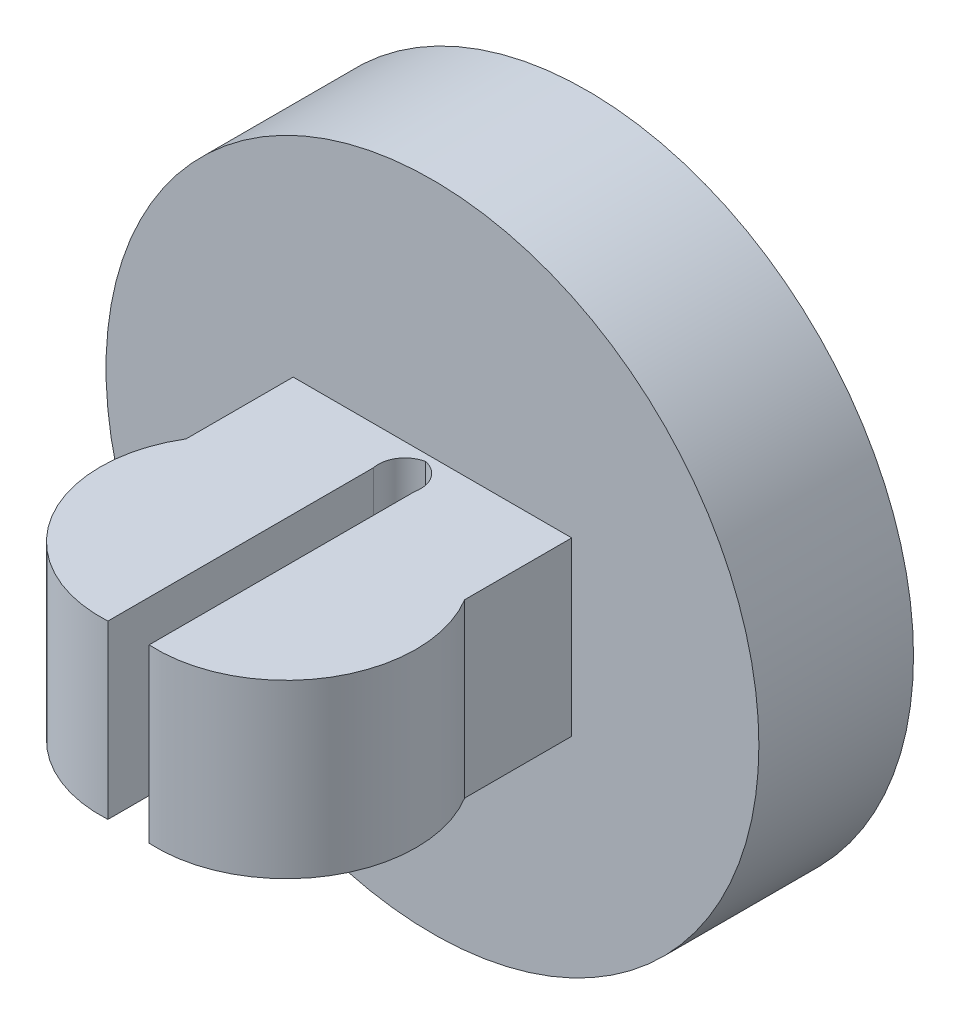
SolidWorks part; units mm, degrees
ref_plane "Front Plane" through (0, 0, 0) normal (0, 0, 1) x (1, 0, 0)
ref_plane "Top Plane" through (0, 0, 0) normal (0, 1, 0) x (1, 0, 0)
ref_plane "Right Plane" through (0, 0, 0) normal (1, 0, 0) x (0, 0, -1)
sketch "Sketch1" plane through (0, 0, 0) normal (0, 0, 1) x (1, 0, 0)
  circle A0 centre (0, 0) radius 9.5
  dimension "D1" = 19
extrude "Boss-Extrude1" add sketch "Sketch1" along normal blind 4.5
sketch "Sketch3" plane through (0, 0, 0) normal (0, 1, 0) x (1, 0, 0)
  line L0 (-9.5, -4.5) -> (9.5, -4.5) construction
  line L1 (0, 0) -> (0, -14.3724) construction
  line L3 (-4.053, -4.5) -> (4.053, -4.5)
  line L6 (-0.6, -5.6201) -> (-0.6, -13.3459)
  line L7 (-4.5469, -7.7337) -> (-4.5469, -11.8821) construction
  line L8 (-4.053, -7.6166) -> (-4.053, -4.5)
  line L9 (4.053, -7.6166) -> (4.053, -4.5)
  line L10 (0.6, -5.6201) -> (0.6, -13.3459)
  arc A1 (-4.053, -7.6166) -> (-0.6, -13.3459) centre (-0.8163, -9.571) ccw
  arc A5 (-0.6, -5.6201) -> (0, -4.7) centre (0.1601, -5.46) cw
  arc A6 (0.6, -5.6201) -> (0, -4.7) centre (-0.1601, -5.46) ccw
  arc A7 (4.053, -7.6166) -> (0.6, -13.3459) centre (0.8163, -9.571) cw
  point P21 (0, -4.5)
  dimension "D1" = 0.4939
  dimension "D2" = 0.6
  dimension "D3" = 4.5469
extrude "Boss-Extrude2" add sketch "Sketch3" along normal mid plane 5
